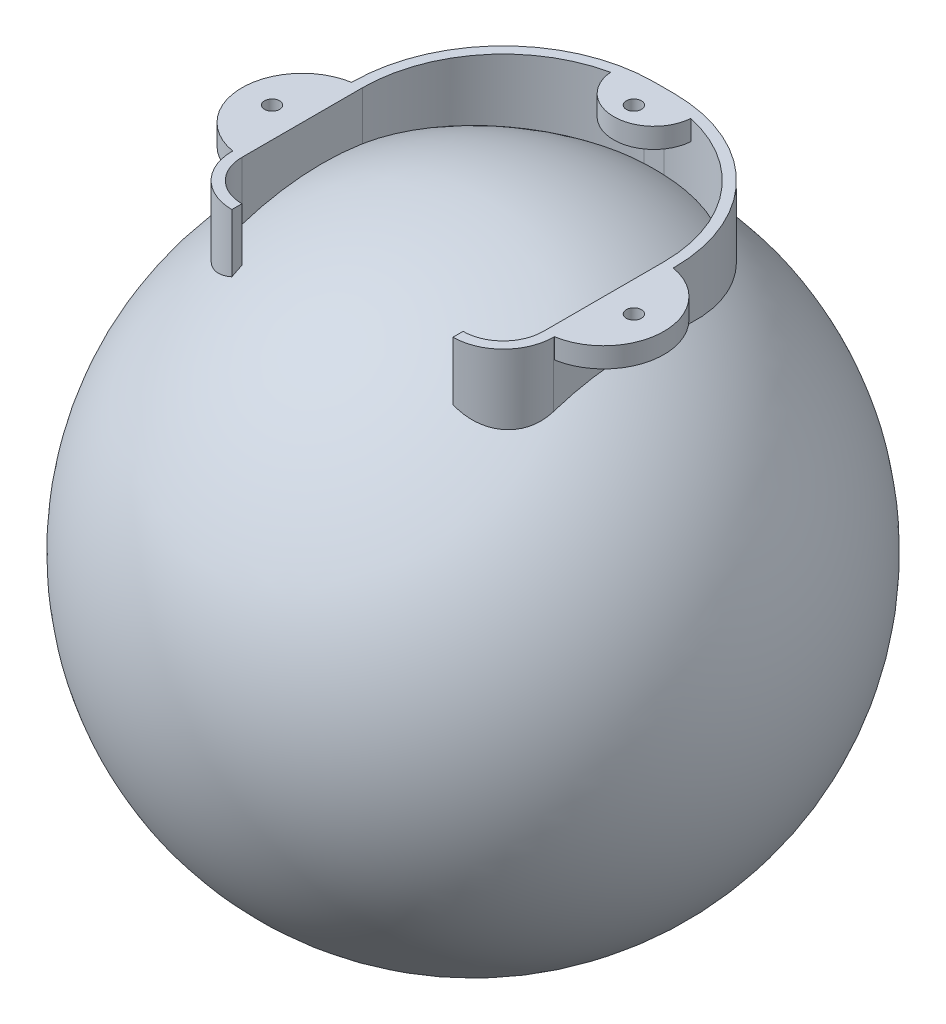
SolidWorks part; units mm, degrees
ref_plane "Front Plane" through (0, 0, 0) normal (0, 0, 1) x (1, 0, 0)
ref_plane "Top Plane" through (0, 0, 0) normal (0, 1, 0) x (1, 0, 0)
ref_plane "Right Plane" through (0, 0, 0) normal (1, 0, 0) x (0, 0, -1)
sketch "Sketch1" plane through (0, 0, 0) normal (0, 1, 0) x (1, 0, 0)
  line L0 (-7.5, -2.5) -> (7.5, -2.5) construction
  line L1 (-0.5, 7.5) -> (0.5, 7.5)
  line L2 (-7.5, 0.5) -> (-7.5, -5.5)
  line L3 (-5.5, -7.5) -> (5.5, -7.5)
  line L4 (7.5, 0.5) -> (7.5, -5.5)
  line L5 (-7.5, 7.5) -> (7.5, -7.5) construction
  line L6 (-7.5, -7.5) -> (7.5, 7.5) construction
  line L7 (0, 7.5) -> (0, -13.8046) construction
  line L8 (-10.5, -2.5) -> (-7.5, -2.5) construction
  line L9 (-9, -2.5) -> (-9, -4.8679) construction
  line L10 (0, 7.5) -> (0, 5.5) construction
  line L11 (0, 5.5) -> (0, 6.5) construction
  line L12 (0, 6.5) -> (-5.5, 6.5) construction
  arc A0 (-0.5, 7.5) -> (-7.5, 0.5) centre (-0.5, 0.5) ccw
  arc A1 (0.5, 7.5) -> (7.5, 0.5) centre (0.5, 0.5) cw
  arc A2 (5.5, -7.5) -> (7.5, -5.5) centre (5.5, -5.5) ccw
  arc A3 (-7.5, -5.5) -> (-5.5, -7.5) centre (-5.5, -5.5) ccw
  arc A4 (-7.5, 0.5) -> (-7.5, -5.5) centre (-7.5, -2.5) ccw
  arc A5 (-1.9935, 7.3388) -> (1.9935, 7.3388) centre (0, 7.5) ccw
  arc A6 (7.5, 0.5) -> (7.5, -5.5) centre (7.5, -2.5) cw
  point P0 (0, 0)
  point P31 (9, -2.5)
  point P32 (-9, -2.5)
  point P37 (0, 6.5)
  point P38 (0, 0)
  dimension "D3" = 7
  dimension "D4" = 2
  dimension "D5" = 3
  dimension "D6" = 2
  dimension "D1" = 15
  dimension "D2" = 15
ref_plane "Plane1" through (0, -5, 0) normal (0, 1, 0) x (1, 0, 0)
sketch "Sketch2" plane through (0, -5, 0) normal (0, 1, 0) x (1, 0, 0)
  line L0 (-5.5, -7.5) -> (5.5, -7.5) construction
  line L1 (-6.5, 12.5) -> (6.5, 12.5)
  line L2 (-7.5, 11.5) -> (-7.5, -5.5)
  line L3 (-5.5, -7.5) -> (5.5, -7.5)
  line L4 (7.5, 11.5) -> (7.5, -5.5)
  line L5 (-7.5, 12.5) -> (7.5, -7.5) construction
  line L6 (-7.5, -7.5) -> (7.5, 12.5) construction
  arc A0 (5.5, -7.5) -> (7.5, -5.5) centre (5.5, -5.5) ccw
  arc A1 (-7.5, -5.5) -> (-5.5, -7.5) centre (-5.5, -5.5) ccw
  arc A2 (6.5, 12.5) -> (7.5, 11.5) centre (6.5, 11.5) cw
  arc A3 (-6.5, 12.5) -> (-7.5, 11.5) centre (-6.5, 11.5) ccw
  point P0 (0, 2.5)
  point P5 (0, -7.5)
  point P8 (0, -7.5)
  dimension "D5" = 2
  dimension "D6" = 1
  dimension "D1" = 0
  dimension "D2" = 0
  dimension "D3" = 15
  dimension "D4" = 20
ref_plane "Plane2" through (0, -2, 0) normal (0, 1, 0) x (1, 0, 0)
sketch "Sketch4" plane through (0, -2, -5) normal (0, 1, 0) x (1, 0, 0)
  line L1 (-5.5, 2.5) -> (5.5, 2.5)
  line L2 (-7.5, 0.5) -> (-7.5, -10.5)
  line L3 (-5.5, -12.5) -> (5.5, -12.5)
  line L4 (7.5, 0.5) -> (7.5, -10.5)
  line L5 (-7.5, 2.5) -> (7.5, -12.5) construction
  line L6 (-7.5, -12.5) -> (7.5, 2.5) construction
  arc A0 (-5.5, 2.5) -> (-7.5, 0.5) centre (-5.5, 0.5) ccw
  arc A1 (5.5, 2.5) -> (7.5, 0.5) centre (5.5, 0.5) cw
  arc A2 (5.5, -12.5) -> (7.5, -10.5) centre (5.5, -10.5) ccw
  arc A3 (-7.5, -10.5) -> (-5.5, -12.5) centre (-5.5, -10.5) ccw
  point P0 (0, -5)
  dimension "D3" = 2
  dimension "D4" = 2
  dimension "D1" = 15
  dimension "D2" = 15
  dimension "D5" = 0
ref_plane "Plane3" through (0, -15.25, 0) normal (0, 1, 0) x (1, 0, 0)
sketch "Sketch7" plane through (0, -15.25, 0) normal (0, 1, 0) x (1, 0, 0)
  line L0 (5.5, -7.5) -> (-5.5, -7.5)
  line L3 (-8.5, 8.25) -> (-8.5, 14.2)
  line L4 (-8.2, 14.5) -> (8.2, 14.5)
  line L5 (8.5, 14.2) -> (8.5, 8.25)
  line L8 (-5.5, -7.5) -> (5.5, -7.5) construction
  line L9 (-5.5, 7.5) -> (5.5, 7.5) construction
  line L11 (-7.25, 14.5) -> (-8.25, 14.5)
  line L12 (-7.25, 14.5) -> (-7.25, 11.5)
  line L13 (-7.25, 11.5) -> (-8.5, 11.5)
  line L14 (-8.5, 14.25) -> (-8.5, 11.5)
  line L15 (-7.25, 14.5) -> (-8.5, 11.5) construction
  line L16 (-7.25, 11.5) -> (-8.5, 14.5) construction
  line L17 (-5.5, 11.5) -> (-8.5, 11.5)
  line L18 (-5.5, 11.5) -> (-5.5, 11)
  line L19 (-5.5, 11) -> (-8.5, 11)
  line L20 (-8.5, 11.5) -> (-8.5, 11)
  line L21 (-5.5, 11.5) -> (-8.5, 11) construction
  line L22 (-5.5, 11) -> (-8.5, 11.5) construction
  arc A0 (-5.5, -7.5) -> (-7.5, -5.5) centre (-5.5, -5.5) cw
  arc A1 (7.4953, -5.3637) -> (5.5, -7.5) centre (5.5, -5.5) cw
  arc A6 (8.2, 14.5) -> (8.5, 14.2) centre (8.2, 14.2) cw
  arc A7 (-8.5, 14.2) -> (-8.2, 14.5) centre (-8.2, 14.2) cw
  arc A8 (7.4953, -5.3637) -> (8.5, 8.25) centre (55.6487, -2.0734) cw
  arc A9 (-7.5, -5.5) -> (-8.5, 8.25) centre (-55.645, -2.0901) ccw
  arc A10 (-8.25, 14.5) -> (-8.5, 14.25) centre (-8.25, 14.25) ccw
  point P0 (0, -7.5)
  point P3 (-7.875, 13)
  point P11 (0, 14.5)
  point P20 (-7.5, -7.5)
  point P23 (7.5, -7.5)
  point P26 (7.5, 7.5)
  point P28 (-7, 11.25)
  point P31 (-7.5, 7.5)
  point P36 (8.5, 14.5)
  point P39 (-8.5, 14.5)
  dimension "D9" = 2
  dimension "D10" = 1.25
  dimension "D11" = 0.3
  dimension "D14" = 0.25
  dimension "D1" = 0
  dimension "D2" = 0
  dimension "D3" = 3
  dimension "D4" = 15
  dimension "D5" = 15
  dimension "D6" = 17
  dimension "D7" = 0
  dimension "D8" = 7
  dimension "D12" = 0
  dimension "D13" = 0
  dimension "D15" = 3
  dimension "D16" = 0.5
  dimension "D17" = 0
  dimension "D18" = 0
sketch "Sketch10" plane through (0, -15.25, 0) normal (0, 1, 0) x (1, 0, 0)
  line L0 (0, 7.5) -> (0, -13.8046) construction
  line L1 (0, -16.5) -> (0, 13.5) construction
  line L2 (0, -16.5) -> (0, 13.5)
  arc A0 (0, -16.5) -> (0, 13.5) centre (0, -1.5) ccw
  point P5 (0, -1.3069)
  point P7 (0, 0)
  dimension "D1" = 30
  dimension "D2" = 1.5
revolve "Revolve1" add sketch "Sketch10" angle 360 about L1
extrude "Extrude-Thin2" add sketch "Sketch1" against normal up to surface (3.6526 mm away) separate body thin contours A1 L4 A2 L3 A3 L2 A0 L1 thin type one direction wall 0.5
extrude "Boss-Extrude5" add sketch "Sketch1<13>" against normal blind 1 contours A6 L4 | A0 A5 A1 L1 | L2 A4 region at (0, 0, -6.6301) region at (-8.7732, 0, 2.5) region at (8.7732, 0, 2.5)
sketch "Sketch1<13>" plane through (0, 0, 0) normal (0, 1, 0) x (1, 0, 0) same geometry as "Sketch1"
hole_wizard "Tap Drill for M1x0.25 Tap3" positions "Sketch15" profile "Sketch16" hole size "M1x0.25" standard "JIS" end condition up to next
sketch "Sketch15" plane through (0, 0, 0) normal (0, 1, 0) x (1, 0, 0)
  point P0 (0, 6.5)
  point P3 (9, -2.5)
  point P6 (-9, -2.5)
sketch "Sketch16" plane through (0, 0, -6.5) normal (1, 0, 0) x (0, 0, 1)
  line L0 (0, 0) -> (0, 2.5614)
  line L1 (0, 2.5614) -> (0.375, 2.5614)
  line L2 (0.375, 2.5614) -> (0.375, 0)
  line L5 (0.375, 0) -> (0, 0)
  line L11 (0, -6.35) -> (0, 107.95) construction
  dimension "Thru Hole Dia." = 0.75
  dimension "Thru Hole Depth" = 2.5614
sketch "Sketch19" plane through (0, 0, 8) normal (0, 0, 1) x (1, 0, 0)
  line L9 (5.5, -2.9009) -> (5.5, 0)
  line L10 (5.5, 0) -> (-5.5, 0)
  line L11 (-5.5, 0) -> (-5.5, -2.9009)
  line L12 (5.5, -2.9009) -> (5.5, 0)
  line L13 (5.5, 0) -> (-5.5, 0)
  line L14 (-5.5, 0) -> (-5.5, -2.9009)
  arc A3 (5.5, -2.9009) -> (-5.5, -2.9009) centre (0, -15.25) ccw
  arc A4 (5.5, -2.9009) -> (-5.5, -2.9009) centre (0, -15.25) ccw
  dimension "D1" = 0
extrude "Cut-Extrude1" cut sketch "Sketch19" against normal up to next (0.5 mm away)
